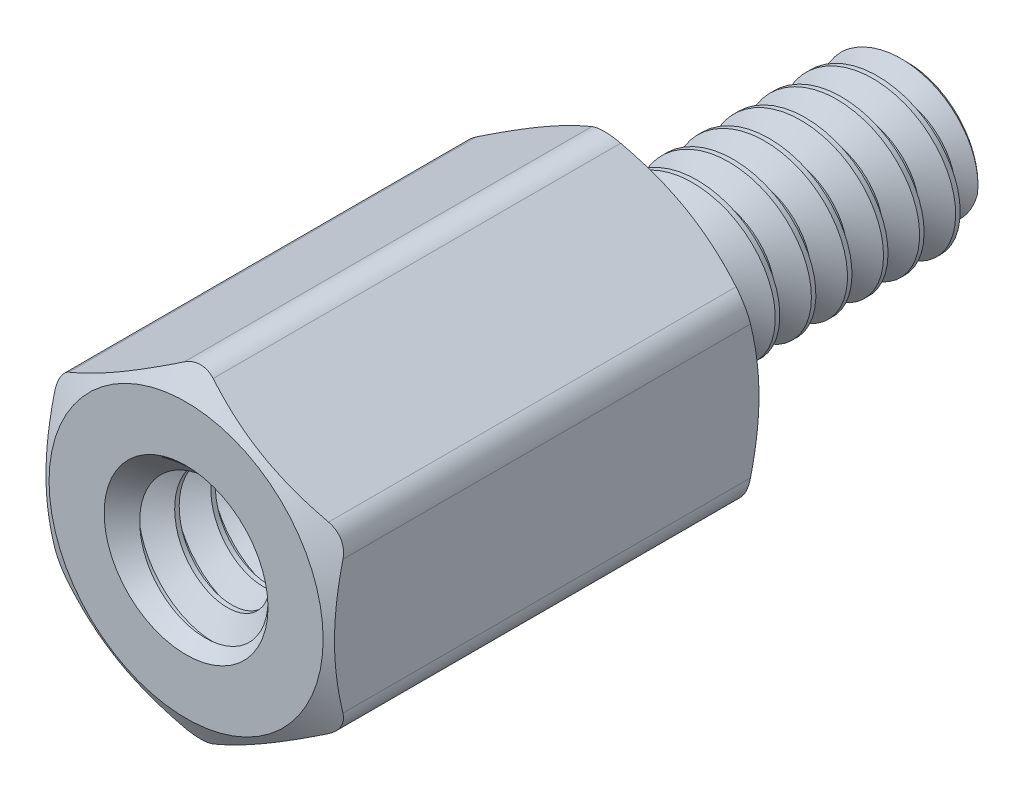
SolidWorks part; units mm, degrees
ref_plane "Front Plane" through (0, 0, 0) normal (0, 0, 1) x (1, 0, 0)
ref_plane "Top Plane" through (0, 0, 0) normal (0, 1, 0) x (1, 0, 0)
ref_plane "Right Plane" through (0, 0, 0) normal (1, 0, 0) x (0, 0, -1)
sketch "Sketch1" plane through (0, 0, 0) normal (0, 0, 1) x (1, 0, 0)
  line L1 (3.175, 1.8331) -> (0, 3.6662)
  line L2 (0, 3.6662) -> (-3.175, 1.8331)
  line L3 (-3.175, 1.8331) -> (-3.175, -1.8331)
  line L4 (-3.175, -1.8331) -> (0, -3.6662)
  line L5 (0, -3.6662) -> (3.175, -1.8331)
  line L6 (3.175, -1.8331) -> (3.175, 1.8331)
  circle A0 centre (0, 0) radius 3.175 construction
  point P10 (0, -3.175)
  dimension "Hex Size" = 6.35
sketch "Sketch2" plane through (0, 0, 0) normal (1, 0, 0) x (0, 0, -1)
  line L0 (6.35, 0) -> (-9.525, 0) construction
  line L2 (0, 1.7526) -> (0, -1.7526) construction
  line L3 (-3.9624, 1.7526) -> (-3.9624, -1.7526) construction
  line L4 (-10.2691, 1.8385) -> (-9.8723, 1.1511) construction
  line L5 (-9.8723, 1.1511) -> (-9.4754, 1.8385) construction
  line L6 (-9.4754, 1.8385) -> (-10.2691, 1.8385) construction
  line L7 (-10.2195, 1.7526) -> (-9.525, 1.7526) construction
  line L8 (-9.9219, 1.237) -> (-9.8227, 1.237) construction
  line L9 (-9.8723, 1.237) -> (-9.8723, 1.1511) construction
  line L10 (-9.8723, 1.7526) -> (-9.8723, 1.8385) construction
  line L11 (6.3004, 1.8385) -> (7.0941, 1.8385) construction
  line L12 (7.0941, 1.8385) -> (6.6973, 1.1511) construction
  line L13 (6.6973, 1.1511) -> (6.3004, 1.8385) construction
  line L14 (6.35, 1.7526) -> (7.0445, 1.7526) construction
  line L15 (6.6477, 1.237) -> (6.7469, 1.237) construction
  line L16 (6.6973, 1.237) -> (6.6973, 1.1511) construction
  line L17 (6.6973, 1.7526) -> (6.6973, 1.8385) construction
  line L18 (0, 3.6662) -> (-9.525, 3.6662) construction
  point P6 (0, 0)
  point P9 (-3.9624, 0)
  dimension "Length" = 9.525
sketch "Sketch3" plane through (0, 0, 0) normal (1, 0, 0) x (0, 0, -1)
  line L0 (-3.9624, 0) -> (6.35, 0)
  line L1 (-3.9624, 1.7526) -> (-3.9624, -1.7526) construction
  line L2 (6.35, 0) -> (6.35, 1.5542)
  line L3 (6.35, 1.5542) -> (6.1516, 1.7526)
  line L4 (6.1516, 1.7526) -> (1.0597, 1.7526)
  line L5 (1.0597, 1.7526) -> (0.762, 1.237)
  line L6 (-3.9624, 0) -> (-3.9624, 1.5542)
  line L7 (-3.9624, 1.5542) -> (-4.1608, 1.7526)
  line L8 (-4.1608, 1.7526) -> (-9.3266, 1.7526)
  line L9 (-9.3266, 1.7526) -> (-9.525, 1.951)
  line L10 (6.1516, 0) -> (6.1516, -1.7526) construction
  line L11 (-9.525, 1.951) -> (-9.525, 3.175)
  line L12 (-9.525, 3.175) -> (0, 3.175)
  line L14 (0.762, 1.237) -> (0.1984, 1.237)
  line L15 (0, 1.4355) -> (0, 3.175)
  arc A0 (0, 1.4355) -> (0.1984, 1.237) centre (0.1984, 1.4355) ccw
  point P5 (-9.525, -3.175)
  point P8 (-7.5406, -1.7526)
  point P9 (4.3656, -1.7526)
  point P27 (0, 1.237)
  dimension "D4" = 0.1984
  dimension "D2" = 0.1984
  dimension "D1" = 45
  dimension "D6" = 1.9844
  dimension "D7" = 60
  dimension "D3" = 1.9844
  dimension "D5" = 0.762
revolve "Revolve1" add sketch "Sketch3" angle 360 about L0 region at (0, 1.5569, 1.3866)
sketch "Sketch4" plane through (0, 0, 9.525) normal (0, 0, 1) x (1, 0, 0)
  line L0 (0, 3.175) -> (0, 1.7526) construction
  line L1 (-3.175, 1.8331) -> (-3.175, -1.8331)
  line L2 (-3.175, -1.8331) -> (0, -3.6662)
  line L3 (0, -3.6662) -> (3.175, -1.8331)
  line L4 (3.175, -1.8331) -> (3.175, 1.8331)
  line L5 (3.175, 1.8331) -> (0, 3.6662)
  line L6 (0, 3.6662) -> (-3.175, 1.8331)
  circle A0 centre (0, 0) radius 3.175 construction
  circle A1 centre (0, 0) radius 2.4638
  circle A2 centre (0, 0) radius 3.175 construction
  point P16 (0, 2.4638)
extrude "Boss-Extrude1" add sketch "Sketch4" against normal up to surface (9.525 mm away) up to face at (0, 3.175, 0)
sketch "Sketch5" plane through (0, 0, 9.525) normal (0, 0, 1) x (1, 0, 0)
  line L0 (-1.0053, 1.4356) -> (1.0053, -1.4356) construction
  line L1 (0, 1.7526) -> (0, -1.7526) construction
  line L3 (0, -2.9435) -> (0, 2.9435) construction
  circle A0 centre (0, 0) radius 3.0162
  point P11 (1.0053, -1.4356)
  dimension "D1" = 6.0325
  dimension "D2" = 35
extrude "Cut-Extrude1" cut sketch "Sketch5" against normal through all draft 60 flip side to cut
sketch "Sketch6" plane through (0, 0, 0) normal (0, 0, -1) x (-1, 0, 0)
  circle A0 centre (0, 0) radius 3.0162
  circle A1 centre (0, 0) radius 3.0162 construction
extrude "Cut-Extrude2" cut sketch "Sketch6" against normal through all draft 60 flip side to cut
fillet "Fillet1" radius 0.635 6 edges at (0, 3.6662, 4.7625) (-3.175, -1.8331, 4.7625) (0, -3.6662, 4.7625) (3.175, -1.8331, 4.7625) (3.175, 1.8331, 4.7625) (-3.175, 1.8331, 4.7625)
sketch "Drawing1" plane through (0, 0, 0) normal (1, 0, 0) x (0, 0, -1)
  line L0 (-9.525, 1.7526) -> (-3.9624, 1.7526) construction
  line L1 (-3.9624, 1.7526) -> (-3.9624, -1.7526) construction
  line L2 (-3.9624, -1.7526) -> (-9.525, -1.7526) construction
sketch "Sketch7" plane through (0, 0, 0) normal (-1, 0, 0) x (0, 0, 1)
  line L0 (-6.6477, 1.237) -> (-6.7469, 1.237)
  line L1 (-6.7469, 1.237) -> (-7.0693, 1.7956)
  line L2 (-7.0941, 1.8385) -> (-6.6973, 1.1511) construction
  line L3 (-7.0693, 1.7956) -> (-6.3252, 1.7956)
  line L4 (-6.6973, 1.1511) -> (-6.3004, 1.8385) construction
  line L5 (-6.3252, 1.7956) -> (-6.6477, 1.237)
  line L6 (-6.6973, 1.7526) -> (-6.6973, 1.8385) construction
  point P12 (-6.6973, 1.7956)
sketch "Sketch8" plane through (0, 0, -6.35) normal (0, 0, -1) x (-1, 0, 0)
  circle A0 centre (0, 0) radius 1.7526
curve "Helix/Spiral1" pitch 0.7937 height 6.1595 radius 1.7526 centre (0, 0, -6.35) axis (0, 0, 1) start towards (0, 1, 0)
sweep "Cut-Sweep1" cut profiles "Sketch7" path "Helix/Spiral1" align with end faces yes
sketch "Sketch9" plane through (0, 0, 3.9624) normal (0, 0, 1) x (1, 0, 0)
  circle A0 centre (0, 0) radius 1.951
extrude "Boss-Extrude2" add sketch "Sketch9" along normal up to surface (5.5626 mm away) up to face at (0, 1.951, 9.525)
sketch "Sketch10" plane through (0, 0, 0) normal (1, 0, 0) x (0, 0, -1)
  line L0 (6.35, 0) -> (-9.525, 0) construction
  line L1 (-3.9624, 1.7526) -> (-9.525, 1.7526)
  line L2 (-3.9624, 1.7526) -> (-3.9624, 0)
  line L3 (-3.9624, 0) -> (-9.525, 0)
  line L4 (-9.525, 1.7526) -> (-9.525, 0)
revolve "Revolve2" add sketch "Sketch10" angle 360 about L0
sketch "Sketch11" plane through (0, 0, 9.525) normal (0, 0, 1) x (1, 0, 0)
  circle A0 centre (0, 0) radius 1.7526
  circle A1 centre (0, 0) radius 1.7526 construction
sketch "Sketch12" plane through (0, 0, 0) normal (1, 0, 0) x (0, 0, -1)
  line L0 (-9.9219, 1.237) -> (-9.8227, 1.237)
  line L1 (-9.8227, 1.237) -> (-9.5002, 1.7956)
  line L2 (-9.8723, 1.1511) -> (-9.4754, 1.8385) construction
  line L3 (-9.5002, 1.7956) -> (-10.2443, 1.7956)
  line L4 (-10.2691, 1.8385) -> (-9.8723, 1.1511) construction
  line L5 (-10.2443, 1.7956) -> (-9.9219, 1.237)
  line L6 (-9.8723, 1.7526) -> (-9.8723, 1.8385) construction
  point P12 (-9.8723, 1.7956)
curve "Helix/Spiral2" pitch 0.7937 height 6.3563 radius 1.7526 centre (0, 0, 9.525) axis (0, 0, -1) start towards (0, 1, 0)
sweep "Cut-Sweep2" cut profiles "Sketch12" path "Helix/Spiral2" align with end faces yes
combine bodies "Combine1" operation type subtract main body 113 bodies to subtract 114
sketch "Sketch13" plane through (0, 0, 9.525) normal (0, 0, 1) x (1, 0, 0)
  circle A0 centre (0, 0) radius 1.8034
  dimension "D1" = 0.0508
extrude "Cut-Extrude3" cut sketch "Sketch13" against normal blind 1.1906 draft 44.759
equation "\"Thread Pitch (B)/8@Sketch2\" = \"Thread Pitch (B)@Sketch2\" / 8"
equation "\"Thread Pitch (A)/8@Sketch2\" = \"Thread Pitch (A)@Sketch2\" / 8"
equation "\"D1@Sketch5\" = \"Hex Size@Sketch1\" * .95"
equation "\"D1@Fillet1\" = \"Hex Size@Sketch1\" * .1"
equation "\"D2@Sketch3\" = \"Thread Pitch (A)@Sketch2\" * .25"
equation "\"D4@Sketch3\" = \"D2@Sketch3\""
equation "\"D6@Sketch3\" = \"Thread Pitch (A)@Sketch2\" * 2.5"
equation "\"D3@Helix/Spiral1\" = \"Thread Length (A)@Sketch2\" - \"D5@Sketch3\" * .25"
equation "\"D4@Helix/Spiral1\" = \"Thread Pitch (A)@Sketch2\""
equation "\"D3@Sketch3\" = \"Thread Pitch (B)@Sketch2\" * 2.5"
equation "\"D5@Sketch3\" = \"Thread Length (A)@Sketch2\" * .12"
equation "\"D3@Helix/Spiral2\" = \"Minimum Thread Length (B)@Sketch2\" + \"Thread Pitch (B)@Sketch2\""
equation "\"D4@Helix/Spiral2\" = \"Thread Pitch (B)@Sketch2\""
equation "\"Pitch Natural Taper Angle\"= ATN ( \"Thread Pitch (B)@Sketch2\" / 2 )"
equation "\"Angle Count\"= 45 / \"Pitch Natural Taper Angle\""
equation "\"Rounded Angle Count\"= ROUND ( \"Angle Count\" )"
equation "\"Taper Angle\"= \"Rounded Angle Count\" * \"Pitch Natural Taper Angle\""
equation "\"D1@Cut-Extrude3\"=\"Thread Pitch (B)@Sketch2\"*1.5"
equation "\"D3@Cut-Extrude3\"=\"Taper Angle\""
